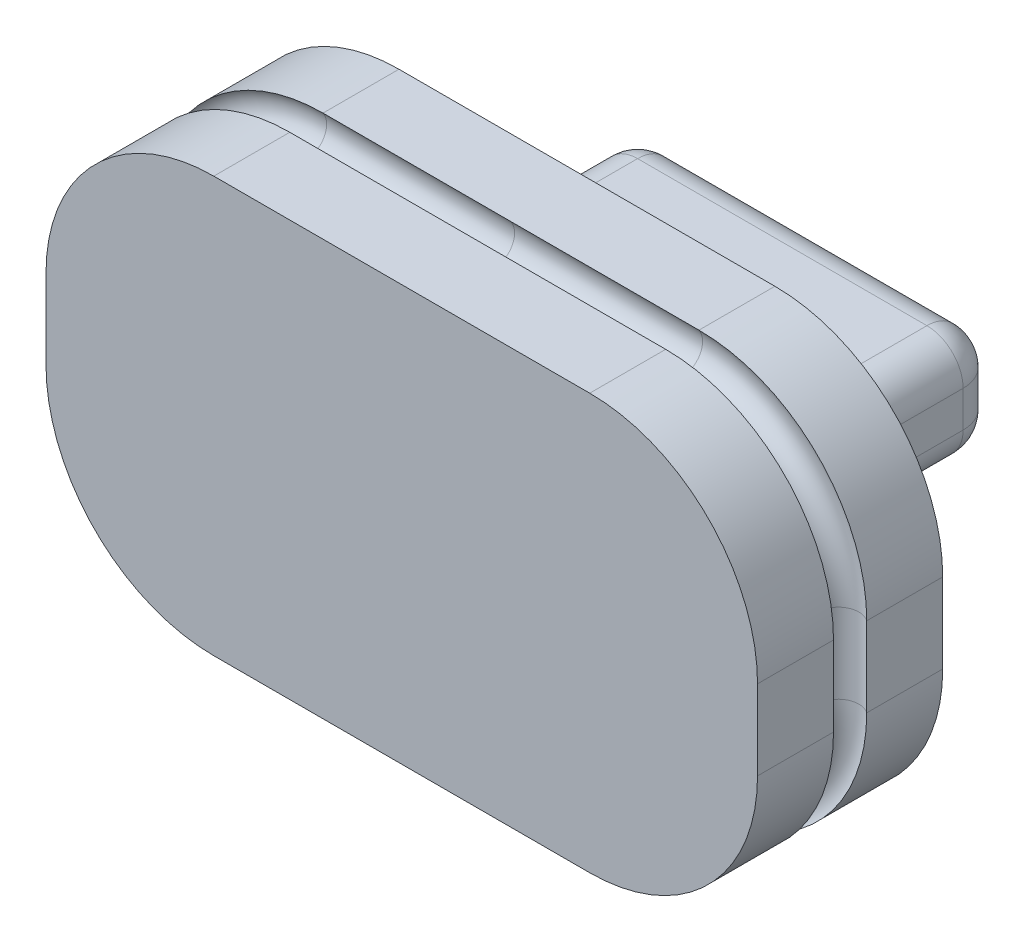
SolidWorks part; units mm, degrees
material "ABS"
ref_plane "X-Y Datum" through (0, 0, 0) normal (0, 0, 1) x (1, 0, 0)
ref_plane "X-Z Datum" through (0, 0, 0) normal (0, 1, 0) x (1, 0, 0)
ref_plane "Y-Z Datum" through (0, 0, 0) normal (1, 0, 0) x (0, 0, -1)
sketch "Sketch1" plane through (0, 0, 0) normal (0, 0, 1) x (1, 0, 0)
  line L12 (-236.0101, 1544.4949) -> (-219.5101, 1544.4949)
  line L13 (-211.5101, 1536.4949) -> (-211.5101, 1532.9949)
  line L14 (-219.5101, 1524.9949) -> (-236.0101, 1524.9949)
  line L15 (-244.0101, 1532.9949) -> (-244.0101, 1536.4949)
  line L16 (-243.3751, 1532.9949) -> (-243.3751, 1536.4949)
  line L17 (-236.0101, 1543.8599) -> (-219.5101, 1543.8599)
  line L18 (-212.1451, 1536.4949) -> (-212.1451, 1532.9949)
  line L19 (-219.5101, 1525.6299) -> (-236.0101, 1525.6299)
  arc A12 (-211.5101, 1536.4949) -> (-219.5101, 1544.4949) centre (-219.5101, 1536.4949) ccw
  arc A13 (-219.5101, 1524.9949) -> (-211.5101, 1532.9949) centre (-219.5101, 1532.9949) ccw
  arc A14 (-244.0101, 1532.9949) -> (-236.0101, 1524.9949) centre (-236.0101, 1532.9949) ccw
  arc A15 (-236.0101, 1544.4949) -> (-244.0101, 1536.4949) centre (-236.0101, 1536.4949) ccw
  arc A16 (-236.0101, 1543.8599) -> (-243.3751, 1536.4949) centre (-236.0101, 1536.4949) ccw
  arc A17 (-212.1451, 1536.4949) -> (-219.5101, 1543.8599) centre (-219.5101, 1536.4949) ccw
  arc A18 (-219.5101, 1525.6299) -> (-212.1451, 1532.9949) centre (-219.5101, 1532.9949) ccw
  arc A19 (-243.3751, 1532.9949) -> (-236.0101, 1525.6299) centre (-236.0101, 1532.9949) ccw
  dimension "D1" = 0.635
extrude "Boss-Extrude1" add sketch "Sketch1" along normal blind 8.128 contours L16 A19 L19 A18 L18 A17 L17 A16 region at (-227.7601, 1534.7449, 0)
sketch "Sketch3" plane through (0, 0, 0) normal (0, 0, -1) x (-1, 0, 0)
  line L0 (243.3751, 1534.7449) -> (212.1451, 1534.7449) construction
  line L4 (234.1101, 1532.3637) -> (221.4101, 1532.3637)
  line L5 (235.6976, 1533.9512) -> (235.6976, 1535.5387)
  line L6 (234.1101, 1537.1262) -> (221.4101, 1537.1262)
  line L7 (219.8226, 1533.9512) -> (219.8226, 1535.5387)
  line L8 (235.6976, 1532.3637) -> (219.8226, 1537.1262) construction
  line L9 (235.6976, 1537.1262) -> (219.8226, 1532.3637) construction
  line L10 (243.3751, 1532.9949) -> (243.3751, 1536.4949) construction
  line L11 (212.1451, 1536.4949) -> (212.1451, 1532.9949) construction
  arc A0 (221.4101, 1537.1262) -> (219.8226, 1535.5387) centre (221.4101, 1535.5387) ccw
  arc A1 (221.4101, 1532.3637) -> (219.8226, 1533.9512) centre (221.4101, 1533.9512) cw
  arc A2 (234.1101, 1532.3637) -> (235.6976, 1533.9512) centre (234.1101, 1533.9512) ccw
  arc A3 (235.6976, 1535.5387) -> (234.1101, 1537.1262) centre (234.1101, 1535.5387) ccw
  point P6 (227.7601, 1534.7449)
  dimension "D3" = 1.5875
  dimension "D1" = 15.875
  dimension "D2" = 4.7625
extrude "Boss-Extrude3" add sketch "Sketch3" along normal blind 10.16
fillet "Fillet1" radius 1.5875 8 edges at (-227.7601, 1537.1262, -10.16) (-235.2326, 1536.6612, -10.16) (-235.6976, 1534.7449, -10.16) (-235.2326, 1532.8286, -10.16) (-227.7601, 1532.3637, -10.16) (-220.2876, 1532.8286, -10.16) (-219.8226, 1534.7449, -10.16) (-220.2876, 1536.6612, -10.16)
ref_plane "Plane1" through (0, 0, 4.064) normal (0, 0, 1) x (1, 0, 0)
ref_plane "Plane2" through (-227.7601, 0, 0) normal (-1, 0, 0) x (0, 0, 1)
sketch "Sketch12" plane through (-227.7601, 0, 0) normal (-1, 0, 0) x (0, 0, 1)
  line L5 (4.064, 1525.6299) -> (4.064, 1543.8599)
  line L6 (8.128, 1525.6299) -> (0, 1525.6299) construction
  line L7 (8.128, 1543.8599) -> (0, 1543.8599) construction
  circle A0 centre (4.064, 1543.3519) radius 0.889
  point P3 (4.064, 1544.2409)
  dimension "D1" = 1.778
  dimension "D2" = 0.381
sketch "Sketch13" plane through (0, 0, 4.064) normal (0, 0, 1) x (1, 0, 0)
  line L4 (-243.3751, 1536.4949) -> (-243.3751, 1532.9949)
  line L5 (-236.0101, 1525.6299) -> (-219.5101, 1525.6299)
  line L6 (-212.1451, 1532.9949) -> (-212.1451, 1536.4949)
  line L7 (-219.5101, 1543.8599) -> (-236.0101, 1543.8599)
  line L8 (-243.3751, 1536.4949) -> (-243.3751, 1532.9949)
  line L9 (-236.0101, 1525.6299) -> (-219.5101, 1525.6299)
  line L10 (-212.1451, 1532.9949) -> (-212.1451, 1536.4949)
  line L11 (-219.5101, 1543.8599) -> (-236.0101, 1543.8599)
  arc A4 (-243.3751, 1532.9949) -> (-236.0101, 1525.6299) centre (-236.0101, 1532.9949) ccw
  arc A5 (-219.5101, 1525.6299) -> (-212.1451, 1532.9949) centre (-219.5101, 1532.9949) ccw
  arc A6 (-212.1451, 1536.4949) -> (-219.5101, 1543.8599) centre (-219.5101, 1536.4949) ccw
  arc A7 (-236.0101, 1543.8599) -> (-243.3751, 1536.4949) centre (-236.0101, 1536.4949) ccw
  arc A8 (-243.3751, 1532.9949) -> (-236.0101, 1525.6299) centre (-236.0101, 1532.9949) ccw
  arc A9 (-219.5101, 1525.6299) -> (-212.1451, 1532.9949) centre (-219.5101, 1532.9949) ccw
  arc A10 (-212.1451, 1536.4949) -> (-219.5101, 1543.8599) centre (-219.5101, 1536.4949) ccw
  arc A11 (-236.0101, 1543.8599) -> (-243.3751, 1536.4949) centre (-236.0101, 1536.4949) ccw
  dimension "D1" = 0
sweep "Cut-Sweep1" cut profiles "Sketch12" path "Sketch13"
